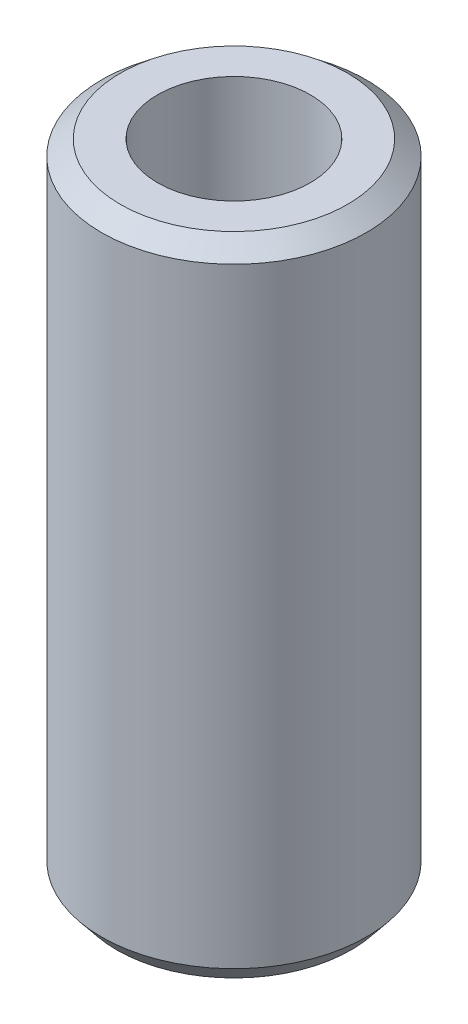
SolidWorks part; units mm, degrees
ref_plane "Front Plane" through (0, 0, 0) normal (0, 0, 1) x (1, 0, 0)
ref_plane "Top Plane" through (0, 0, 0) normal (0, 1, 0) x (1, 0, 0)
ref_plane "Right Plane" through (0, 0, 0) normal (1, 0, 0) x (0, 0, -1)
sketch "Sketch1" plane through (0, 0, 0) normal (0, 1, 0) x (1, 0, 0)
  circle A0 centre (0, 0) radius 47.5
  dimension "SHAFT_OD" = 95
extrude "Boss-Extrude1" add sketch "Sketch1" along normal blind 231.0381
sketch "Sketch2" plane through (0, 0, 0) normal (0, 1, 0) x (1, 0, 0)
  circle A0 centre (0, 0) radius 27.3941
  dimension "BORE_D" = 54.7881
extrude "Cut-Extrude1" cut sketch "Sketch2" along normal through all
chamfer "Chamfer1" distance 5.4225 angle 51.094 2 edges at (0, 231.0381, 47.5) (0, 0, 47.5) first distance on face at (0, 231.0381, 47.5) first distance on face at (0, 0, 27.3941)
